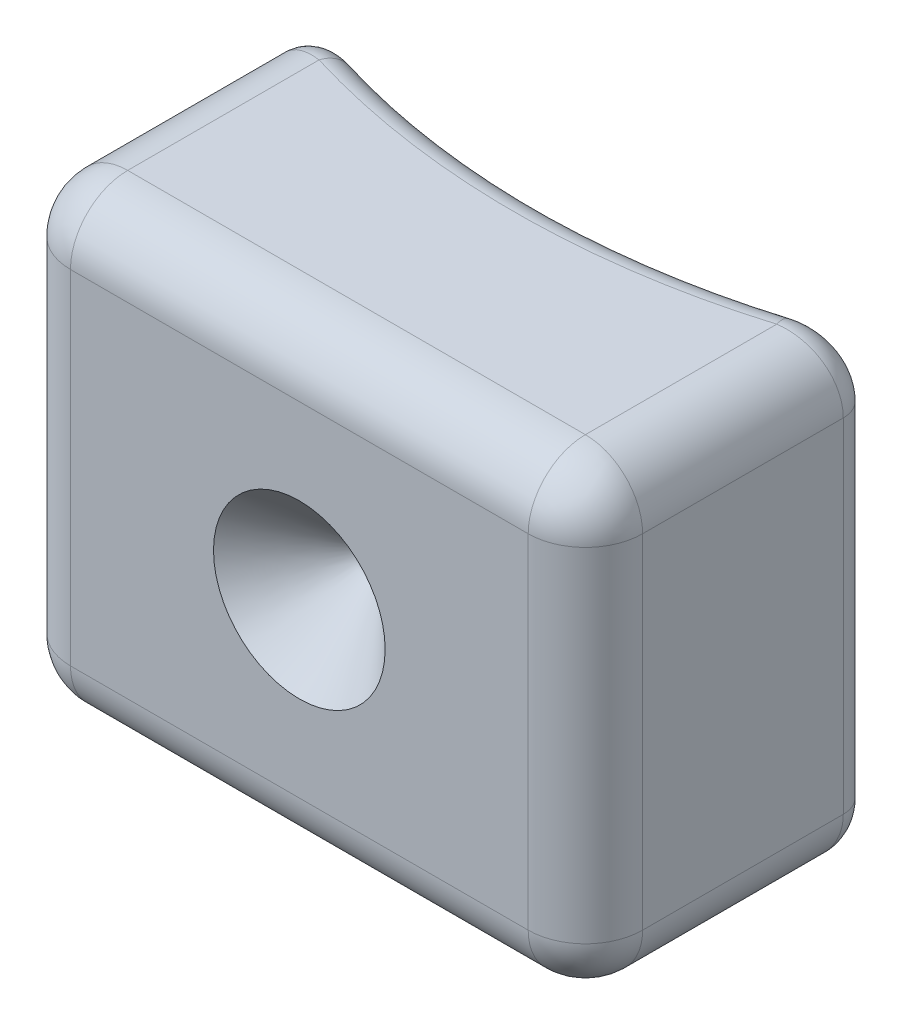
SolidWorks part; units mm, degrees
material "ABS"
ref_plane "Płaszczyzna przednia" through (0, 0, 0) normal (0, 0, 1) x (1, 0, 0)
ref_plane "Płaszczyzna górna" through (0, 0, 0) normal (0, 1, 0) x (1, 0, 0)
ref_plane "Płaszczyzna prawa" through (0, 0, 0) normal (1, 0, 0) x (0, 0, -1)
sketch "Szkic1" plane through (0, 0, 0) normal (0, 1, 0) x (1, 0, 0)
  line L0 (-10, 0) -> (10, 0)
  line L1 (10, 0) -> (10, 10.4592)
  line L2 (0, 0) -> (0, 35) construction
  line L3 (-10, 0) -> (-10, 10.4592)
  arc A0 (-10, 10.4592) -> (10, 10.4592) centre (0, 35) ccw
  dimension "D5" = 53
  dimension "D1" = 90
  dimension "D2" = 10
  dimension "D4" = 35
extrude "Dodanie-wyciągnięcie1" add sketch "Szkic1" along normal blind 16
sketch "Szkic2" plane through (0, 0, 0) normal (0, 0, 1) x (1, 0, 0)
  line L0 (-10, 0) -> (10, 0) construction
  line L1 (-10, 16) -> (-10, 0) construction
  circle A0 centre (0, 8) radius 3
  dimension "D3" = 6
  dimension "D1" = 8
  dimension "D2" = 10
extrude "Wytnij-wyciągnięcie1" cut sketch "Szkic2" against normal blind 12 draft 45
fillet "Zaokrąglenie1" radius 2 8 edges at (-10, 0, -5.2296) (-10, 16, -5.2296) (10, 16, -5.2296) (10, 0, -5.2296) (10, 8, 0) (0, 0, 0) (0, 16, 0) (-10, 8, 0)
fillet "Zaokrąglenie2" radius 1 8 edges at (9.6119, 0.8161, -10.3046) (10, 8, -10.4592) (9.3034, 15.5169, -10.1868) (0, 16, -8.5) (-9.6119, 15.1839, -10.3046) (-10, 8, -10.4592) (-9.3034, 0.4831, -10.1868) (0, 0, -8.5)
